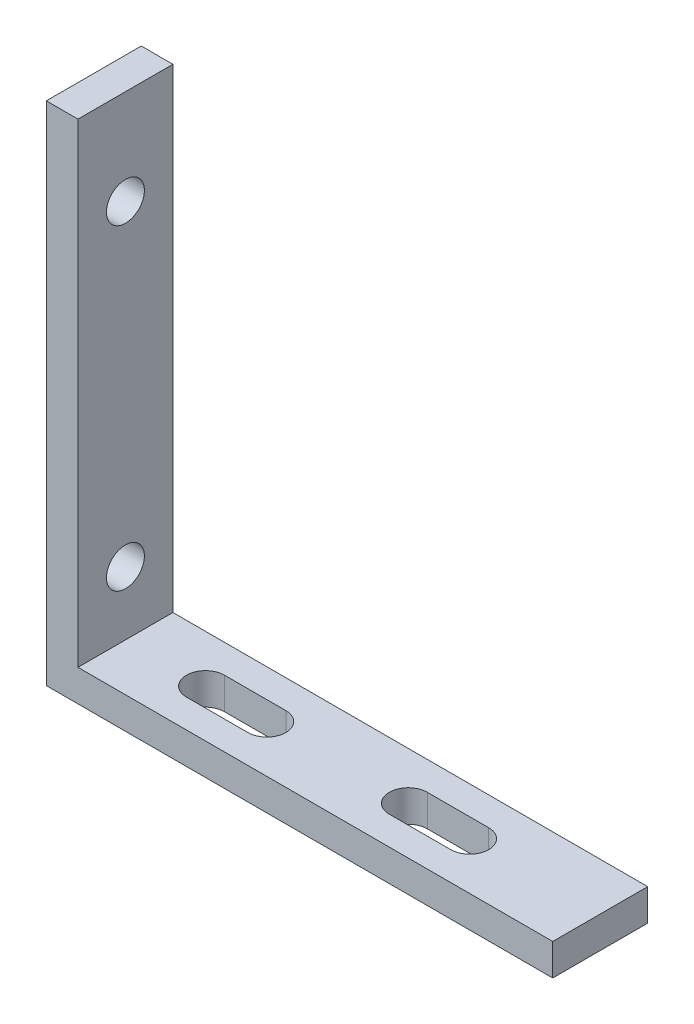
SolidWorks part; units mm, degrees
ref_plane "Front Plane" through (0, 0, 0) normal (0, 0, 1) x (1, 0, 0)
ref_plane "Top Plane" through (0, 0, 0) normal (0, 1, 0) x (1, 0, 0)
ref_plane "Right Plane" through (0, 0, 0) normal (1, 0, 0) x (0, 0, -1)
sketch "Sketch1" plane through (0, 0, 0) normal (0, 1, 0) x (1, 0, 0)
  line L1 (-30.1722, 4.0464) -> (49.8278, 4.0464)
  line L2 (-30.1722, 4.0464) -> (-30.1722, -10.9536)
  line L3 (-30.1722, -10.9536) -> (49.8278, -10.9536)
  line L4 (49.8278, 4.0464) -> (49.8278, -10.9536)
  dimension "D1" = 15
  dimension "D2" = 80
extrude "Boss-Extrude1" add sketch "Sketch1" along normal blind 5
sketch "Sketch3" plane through (0, 5, 0) normal (0, 1, 0) x (1, 0, 0)
  line L0 (-30.1722, 4.0464) -> (-25.1722, 4.0464)
  line L1 (49.8278, 4.0464) -> (-30.1722, 4.0464) construction
  line L2 (-30.1722, -10.9536) -> (-25.1722, -10.9536)
  line L3 (-30.1722, -10.9536) -> (49.8278, -10.9536) construction
  line L4 (-25.1722, 4.0464) -> (-25.1722, -10.9536)
  line L5 (-30.1722, 4.0464) -> (-30.1722, -10.9536)
extrude "Boss-Extrude2" add sketch "Sketch3" along normal blind 75
sketch "Sketch4" plane through (-30.1722, 0, 0) normal (-1, 0, 0) x (0, 0, 1)
  line L0 (3.4536, 80) -> (3.4536, 0)
  line L1 (-4.0464, 80) -> (10.9536, 80) construction
  line L2 (-4.0464, 0) -> (10.9536, 0) construction
  line L3 (3.4536, 0) -> (3.4536, 15)
  line L4 (3.4536, 80) -> (3.4536, 65)
  point P8 (0, 0)
hole_wizard "Ø6.0mm Dowel Hole1" positions "Sketch5" profile "Sketch6" hole size "Ø6.0" standard "ANSI Metric" end condition up to next
sketch "Sketch5" plane through (-30.1722, 0, 0) normal (-1, 0, 0) x (0, 0, 1)
  point P0 (3.4536, 65)
  point P3 (3.4536, 15)
sketch "Sketch6" plane through (-30.1722, 65, 3.4536) normal (0, 1, 0) x (0, 0, 1)
  line L0 (0, 0) -> (0, 5)
  line L1 (0, 5) -> (3, 5)
  line L2 (3, 5) -> (3, 0)
  line L5 (3, 0) -> (0, 0)
  line L11 (0, -6.35) -> (0, 107.95) construction
  dimension "Thru Hole Dia." = 6
  dimension "Thru Hole Depth" = 5
sketch "Sketch7" plane through (0, 0, 0) normal (0, -1, 0) x (1, 0, 0)
  line L0 (-30.1722, 3.4536) -> (49.8278, 3.4536)
  line L1 (-30.1722, -4.0464) -> (-30.1722, 10.9536) construction
  line L2 (49.8278, 10.9536) -> (49.8278, -4.0464) construction
hole_wizard "Ø6.0mm Dowel Slot1" positions "Sketch8" profile "Sketch9" size "Ø6.0" standard "ANSI Metric" slot yes end condition up to next
sketch "Sketch8" plane through (0, 5, 0) normal (0, 1, 0) x (1, 0, 0)
  line L0 (-15.5307, -3.4536) -> (0.1693, -3.4536) construction
  point P0 (-7.6807, -3.4536)
  point P5 (24.3593, -3.4534)
  dimension "D1" = 15.7
sketch "Sketch9" plane through (-7.6807, 5, 3.4536) normal (1, 0, 0) x (0, 0, 1)
  line L0 (0, 0) -> (0, 5)
  line L1 (0, 5) -> (3, 5)
  line L2 (3, 5) -> (3, 0)
  line L5 (3, 0) -> (0, 0)
  line L11 (0, -6.35) -> (0, 107.95) construction
  dimension "Thru Hole Dia." = 6
  dimension "Thru Hole Depth" = 5
